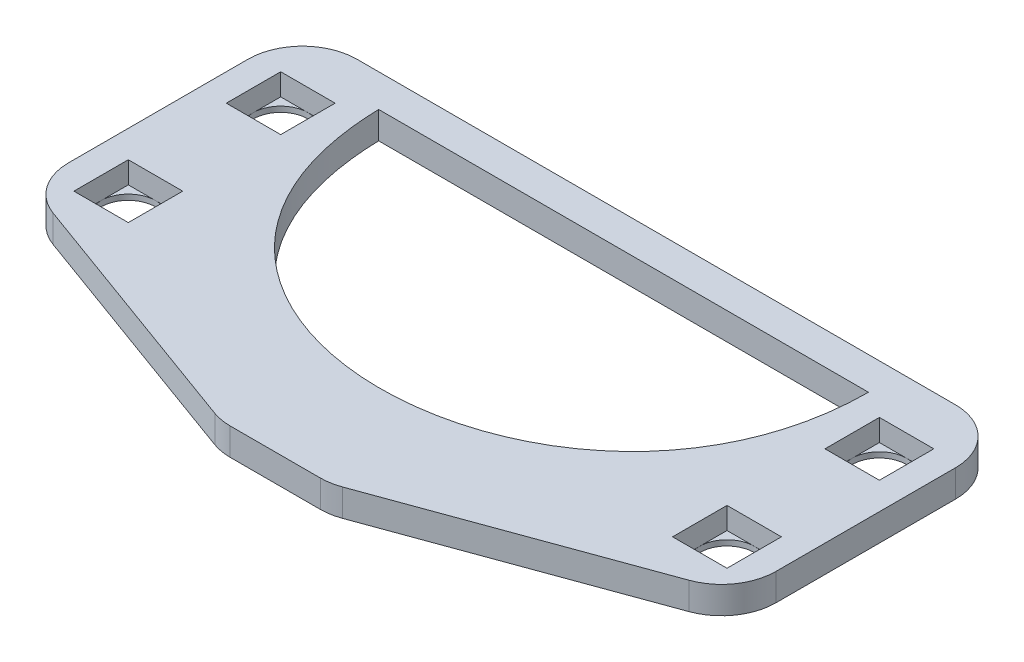
SolidWorks part; units mm, degrees
ref_plane "Front Plane" through (0, 0, 0) normal (0, 0, 1) x (1, 0, 0)
ref_plane "Top Plane" through (0, 0, 0) normal (0, 1, 0) x (1, 0, 0)
ref_plane "Right Plane" through (0, 0, 0) normal (1, 0, 0) x (0, 0, -1)
sketch "Sketch1" plane through (0, 0, 0) normal (0, 1, 0) x (1, 0, 0)
  line L1 (0, 0) -> (65, 0)
  line L2 (0, 0) -> (0, 35)
  line L3 (0, 35) -> (65, 35)
  line L4 (65, 0) -> (65, 35)
  dimension "D1" = 65
  dimension "D2" = 35
extrude "Boss-Extrude1" add sketch "Sketch1" along normal blind 2.5
sketch "Sketch2" plane through (0, 2.5, 0) normal (0, 1, 0) x (1, 0, 0)
  line L0 (10, 32) -> (55, 32)
  line L1 (0, 35) -> (0, 0) construction
  line L2 (65, 35) -> (0, 35) construction
  line L3 (65, 0) -> (65, 35) construction
  line L5 (7.5, 30.5) -> (2.5, 30.5)
  line L6 (7.5, 30.5) -> (7.5, 25.5)
  line L7 (7.5, 25.5) -> (2.5, 25.5)
  line L8 (2.5, 30.5) -> (2.5, 25.5)
  line L9 (7.5, 30.5) -> (2.5, 25.5) construction
  line L10 (7.5, 25.5) -> (2.5, 30.5) construction
  line L11 (7.5, 16.5) -> (2.5, 16.5)
  line L12 (7.5, 16.5) -> (7.5, 11.5)
  line L13 (7.5, 11.5) -> (2.5, 11.5)
  line L14 (2.5, 16.5) -> (2.5, 11.5)
  line L15 (7.5, 16.5) -> (2.5, 11.5) construction
  line L16 (7.5, 11.5) -> (2.5, 16.5) construction
  line L17 (57.5, 16.5) -> (62.5, 16.5)
  line L18 (57.5, 16.5) -> (57.5, 11.5)
  line L19 (57.5, 11.5) -> (62.5, 11.5)
  line L20 (62.5, 16.5) -> (62.5, 11.5)
  line L21 (57.5, 16.5) -> (62.5, 11.5) construction
  line L22 (57.5, 11.5) -> (62.5, 16.5) construction
  line L23 (57.5, 30.5) -> (62.5, 30.5)
  line L24 (57.5, 30.5) -> (57.5, 25.5)
  line L25 (57.5, 25.5) -> (62.5, 25.5)
  line L26 (62.5, 30.5) -> (62.5, 25.5)
  line L27 (57.5, 30.5) -> (62.5, 25.5) construction
  line L28 (57.5, 25.5) -> (62.5, 30.5) construction
  circle A0 centre (5, 28) radius 2.5
  circle A1 centre (5, 14) radius 2.5
  circle A2 centre (60, 28) radius 2.5
  circle A3 centre (60, 14) radius 2.5
  spline S0 degree 3 poles (55, 32) (54.8405, 3.2787) (10.7249, 1.7168) (10, 32) knots 0 0 0 0 1 1 1 1
  dimension "D3" = 3
  dimension "D5" = 5
  dimension "D6" = 5
  dimension "D7" = 5
  dimension "D8" = 5
  dimension "D1" = 45
  dimension "D2" = 10
  dimension "D4" = 14
  dimension "D9" = 5
  dimension "D10" = 5
  dimension "D11" = 7
  dimension "D12" = 5
  dimension "D13" = 5
  dimension "D14" = 5
  dimension "D15" = 5
  dimension "D16" = 5
  dimension "D17" = 5
  dimension "D18" = 5
  dimension "D19" = 5
extrude "Cut-Extrude1" cut sketch "Sketch2" against normal through all contours A0 | A0 | A1 | A3 | A2 | S0 L0 region at (5, 2.5, -28)
extrude "Cut-Extrude2" cut sketch "Sketch2<3>" against normal blind 2 contours A1 L13 L12 | A1 L12 L11 | A1 L11 L14 | A1 L14 L13 | A0 L5 L8 | A0 L6 L5 | A0 L7 L6 | A0 L8 L7 | A2 L23 L24 | A2 L26 L23 | A2 L25 L26 | A2 L24 L25 | A3 L19 L20 | A3 L18 L19 | A3 L17 L18 | A3 L20 L17 region at (6.9416, 2.5, -29.9416) region at (3.0584, 2.5, -29.9416) region at (6.9416, 2.5, -26.0584) region at (3.0584, 2.5, -26.0584) region at (6.9416, 2.5, -15.9416) region at (3.0584, 2.5, -15.9416) region at (6.9416, 2.5, -12.0584) region at (3.0584, 2.5, -12.0584) region at (58.0584, 2.5, -15.9416) region at (61.9416, 2.5, -15.9416) region at (58.0584, 2.5, -12.0584) region at (61.9416, 2.5, -12.0584) region at (58.0584, 2.5, -29.9416) region at (61.9416, 2.5, -29.9416) region at (58.0584, 2.5, -26.0584) region at (61.9416, 2.5, -26.0584)
sketch "Sketch2<3>" plane through (0, 2.5, 0) normal (0, 1, 0) x (1, 0, 0) same geometry as "Sketch2"
chamfer "Chamfer1" distance 10 angle 70 2 edges at (65, 1.25, 0) (0, 1.25, 0) first distance on face at (65, 1.25, -17.5) first distance on face at (0, 1.25, -17.5)
fillet "Fillet1" radius 5 6 edges at (27.4748, 1.25, 0) (37.5252, 1.25, 0) (65, 1.25, -10) (65, 1.25, -35) (0, 1.25, -35) (0, 1.25, -10)
